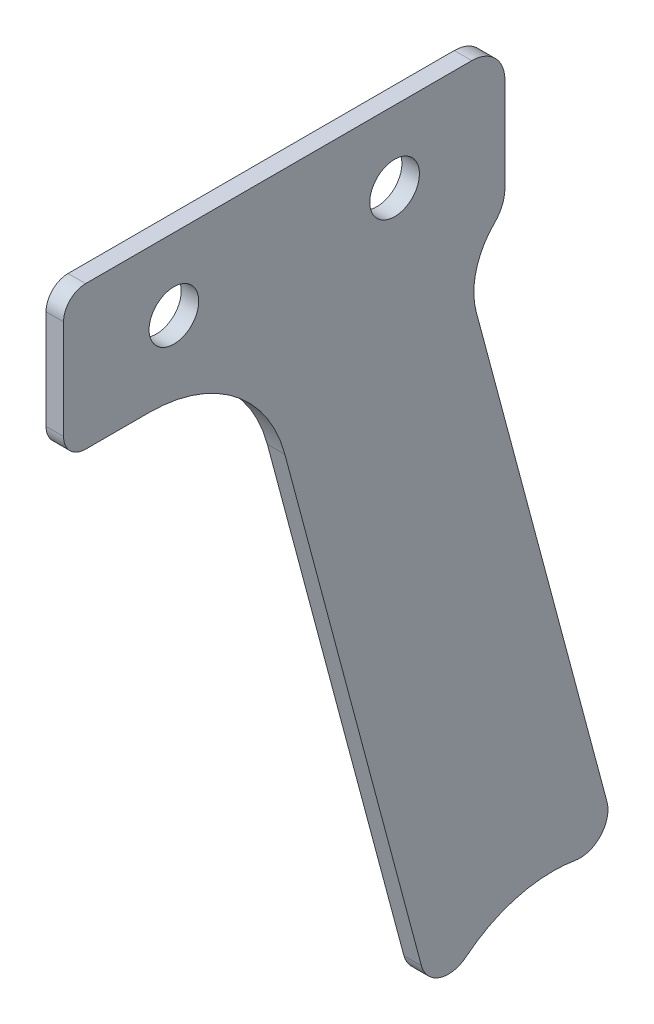
SolidWorks part; units mm, degrees
material "ASTM A36 Steel"
ref_plane "X-Y Datum" through (0, 0, 0) normal (0, 0, 1) x (1, 0, 0)
ref_plane "X-Z Datum" through (0, 0, 0) normal (0, 1, 0) x (1, 0, 0)
ref_plane "Y-Z Datum" through (0, 0, 0) normal (1, 0, 0) x (0, 0, -1)
sketch "Sketch1" plane through (0, 0, 0) normal (1, 0, 0) x (0, 0, -1)
  line L0 (862.4578, 473.6207) -> (843.5366, 544.4607)
  line L1 (866.3223, 474.6529) -> (847.7489, 544.1908)
  line L2 (865.6079, 544.7651) -> (883.1548, 479.0703)
  line L3 (866.0656, 543.0515) -> (883.1548, 479.0703) construction
  line L4 (869.6989, 544.9493) -> (887.0193, 480.1025)
  line L5 (866.3223, 474.6529) -> (847.5018, 545.1159) construction
  line L7 (870.2263, 544.1324) -> (870.2263, 554.1324)
  line L13 (832.2263, 557.1324) -> (867.2263, 557.1324)
  line L15 (830.2263, 546.1324) -> (830.2263, 555.1324)
  line L17 (832.2263, 544.1324) -> (870.2263, 544.1324)
  line L18 (862.4578, 473.6207) -> (843.6373, 544.0837) construction
  line L19 (869.9301, 544.0837) -> (887.0193, 480.1025) construction
  arc A1 (870.2263, 554.1324) -> (867.2263, 557.1324) centre (867.2263, 554.1324) ccw
  arc A3 (832.2263, 557.1324) -> (830.2263, 555.1324) centre (832.2263, 555.1324) ccw
  arc A5 (830.2263, 546.1324) -> (832.2263, 544.1324) centre (832.2263, 546.1324) ccw
  spline S1 degree 3 poles (870.6248, 489.203) (894.7213, 497.2352) (902.9489, 472.5524) (878.8523, 464.5202) (854.7558, 456.488) (846.5282, 481.1708) (870.6248, 489.203) (894.7213, 497.2352) (902.9489, 472.5524) knots -0.5 0 0 0 0.5 0.5 0.5 1 1 1 1.5 1.5 1.5 weights 1 0.333333 0.333333 1 0.333333 0.333333 1 0.333333 0.333333 only from (870.6248, 489.203) to (870.6248, 489.203)
  dimension "D1" = 4
extrude "Boss-Extrude1" add sketch "Sketch1" against normal blind 1.5875
fillet "Fillet1" radius 2.54 2 edges at (-0.7937, 488.2368, -880.7064) (-0.7937, 483.7963, -863.8801)
hole_wizard "M4 Clearance Hole1" positions "Sketch4" profile "Sketch3" hole size "M4" standard "ANSI Metric" end condition through all
sketch "Sketch4" plane through (-1.5875, 0, 0) normal (-1, 0, 0) x (0, 0, 1)
  point P0 (-860.2263, 550.6324)
  point P2 (-840.2263, 550.6324)
sketch "Sketch3" plane through (-1.5875, 550.6324, -860.2263) normal (0, 1, 0) x (0, 0, 1)
  line L0 (0, 0) -> (0, 1.5875)
  line L1 (0, 1.5875) -> (2.25, 1.5875)
  line L2 (2.25, 1.5875) -> (2.25, 0)
  line L5 (2.25, 0) -> (0, 0)
  line L11 (0, -6.35) -> (0, 107.95) construction
  dimension "Thru Hole Dia." = 4.5
  dimension "Thru Hole Depth" = 1.5875
fillet "Fillet2" radius 6.35 1 edges at (-0.7937, 544.1324, -865.7769)
fillet "Fillet3" radius 12.7 1 edges at (-0.7937, 544.1324, -847.7645)
fillet "Fillet4" radius 3.175 1 edges at (-0.7937, 544.1324, -870.2263)
